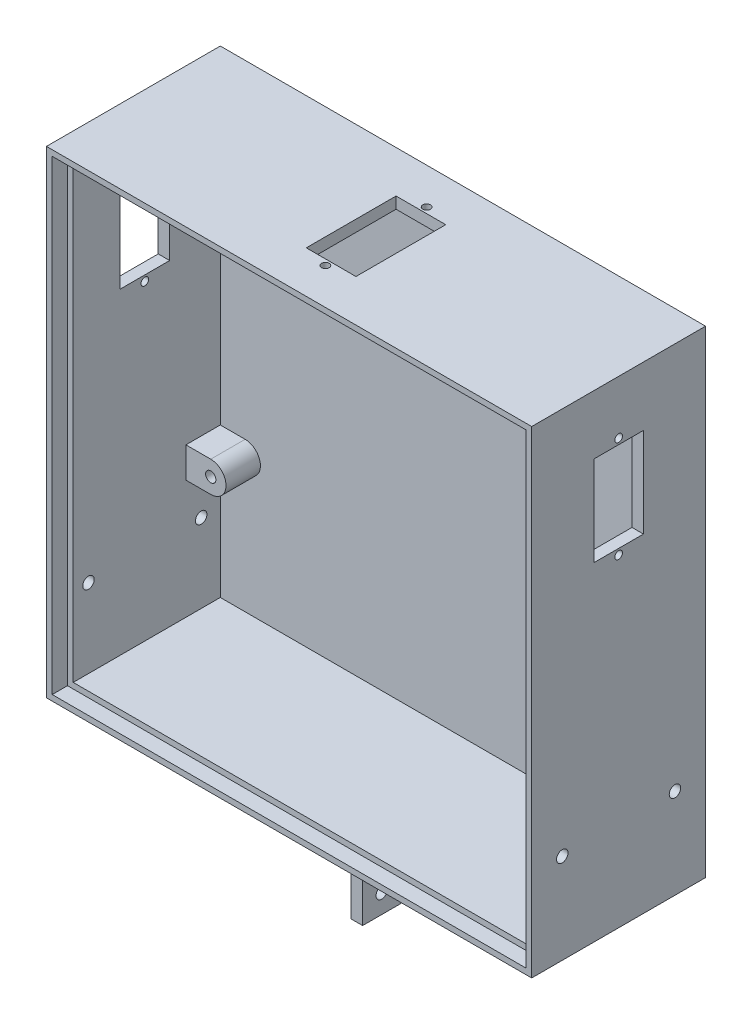
SolidWorks part; units mm, degrees
ref_plane "Front Plane" through (0, 0, 0) normal (0, 0, 1) x (1, 0, 0)
ref_plane "Top Plane" through (0, 0, 0) normal (0, 1, 0) x (1, 0, 0)
ref_plane "Right Plane" through (0, 0, 0) normal (1, 0, 0) x (0, 0, -1)
sketch "Sketch1" plane through (0, 0, 0) normal (0, 0, 1) x (1, 0, 0)
  line L1 (63.5, 62.5) -> (-63.5, 62.5)
  line L2 (63.5, 62.5) -> (63.5, -62.5)
  line L3 (63.5, -62.5) -> (-63.5, -62.5)
  line L4 (-63.5, 62.5) -> (-63.5, -62.5)
  line L5 (63.5, 62.5) -> (-63.5, -62.5) construction
  line L6 (63.5, -62.5) -> (-63.5, 62.5) construction
  point P0 (0, 0)
  dimension "D1" = 127
  dimension "D2" = 125
extrude "Boss-Extrude1" add sketch "Sketch1" along normal blind 45.5
sketch "Sketch2" plane through (0, 0, 45.5) normal (0, 0, 1) x (1, 0, 0)
  line L0 (-63.5, 62.5) -> (-63.5, -62.5) construction
  line L1 (60.5, 59.5) -> (-60.5, 59.5)
  line L2 (60.5, 59.5) -> (60.5, -59.5)
  line L3 (60.5, -59.5) -> (-60.5, -59.5)
  line L4 (-60.5, 59.5) -> (-60.5, -59.5)
  line L5 (60.5, 59.5) -> (-60.5, -59.5) construction
  line L6 (60.5, -59.5) -> (-60.5, 59.5) construction
  line L7 (63.5, 62.5) -> (-63.5, 62.5) construction
  line L9 (62, 61) -> (-62, 61)
  line L10 (62, 61) -> (62, -61)
  line L11 (62, -61) -> (-62, -61)
  line L12 (-62, 61) -> (-62, -61)
  line L13 (62, 61) -> (-62, -61) construction
  line L14 (62, -61) -> (-62, 61) construction
  point P0 (0, 0)
  point P10 (0, 0)
  dimension "D1" = 3
  dimension "D2" = 3
  dimension "D3" = 1.5
  dimension "D4" = 1.5
extrude "Cut-Extrude1" cut sketch "Sketch2" against normal offset from surface (42.5 mm away) 3 contours L1 L4 L3 L2 region at (0, 0, 45.5) up to face at (0, 0, 0)
extrude "Cut-Extrude2" cut sketch "Sketch2<3>" against normal blind 4
sketch "Sketch2<3>" plane through (0, 0, 45.5) normal (0, 0, 1) x (1, 0, 0) same geometry as "Sketch2"
sketch "Sketch3" plane through (0, 0, 3) normal (0, 0, 1) x (1, 0, 0)
  line L0 (35, 53) -> (35, 59.5)
  line L1 (60.5, 59.5) -> (-60.5, 59.5) construction
  line L2 (43, 53) -> (43, 59.5)
  line L3 (60.5, 59.5) -> (-60.5, 59.5) construction
  line L4 (0, -25.025) -> (0, 25.025) construction
  arc A0 (35, 53) -> (43, 53) centre (39, 53) ccw
  circle A2 centre (39, 53) radius 1.35
  line M3 (60.5, 59.5) -> (-60.5, 59.5)
  dimension "D2" = 4
  dimension "D3" = 2.7
  dimension "D1" = 6.5
  dimension "D4" = 39
extrude "Boss-Extrude2" add sketch "Sketch3" along normal blind 9 contours L0 A0 L2 A2 M3 region at (39, 54.7692, 3)
mirror "Mirror1" about plane through (0, 0, 0) normal (1, 0, 0) of "Boss-Extrude2"
sketch "Sketch4" plane through (0, 0, 3) normal (0, 0, 1) x (1, 0, 0)
  line L0 (54, -20.4) -> (60.5, -20.4)
  line L1 (60.5, 59.5) -> (60.5, -59.5) construction
  line L2 (54, -28.4) -> (60.5, -28.4)
  arc A0 (54, -20.4) -> (54, -28.4) centre (54, -24.4) ccw
  circle A1 centre (54, -24.4) radius 1.35
  circle A2 centre (39, 53) radius 1.35 construction
  line M9 (60.5, -59.5) -> (60.5, 59.5)
  dimension "D2" = 4
  dimension "D3" = 2.7
  dimension "D4" = 77.4
  dimension "D1" = 6.5
extrude "Boss-Extrude3" add sketch "Sketch4" along normal blind 9 contours L0 A0 L2 A1 M9 region at (55.7692, -24.4, 3)
mirror "Mirror2" about plane through (0, 0, 0) normal (1, 0, 0) of "Boss-Extrude3"
sketch "Sketch5" plane through (0, 62.5, 0) normal (0, 1, 0) x (1, 0, 0)
  line L0 (0, -22.75) -> (6.5, -22.75) construction
  line L1 (6.5, -11) -> (-6.5, -11)
  line L2 (6.5, -11) -> (6.5, -34.5)
  line L3 (6.5, -34.5) -> (-6.5, -34.5)
  line L4 (-6.5, -11) -> (-6.5, -34.5)
  line L5 (6.5, -11) -> (-6.5, -34.5) construction
  line L6 (6.5, -34.5) -> (-6.5, -11) construction
  line L7 (63.5, -45.5) -> (63.5, 0) construction
  circle A0 centre (0, -9.5) radius 1
  circle A1 centre (0, -36) radius 1
  point P0 (0, -22.75)
  point P8 (0, -11)
  point P12 (63.5, -22.75)
  dimension "D3" = 2
  dimension "D1" = 13
  dimension "D2" = 23.5
  dimension "D4" = 1.5
extrude "Cut-Extrude5" cut sketch "Sketch5" against normal up to surface (3 mm away) up to face at (0, 59.5, 12.4167)
sketch "Sketch7" plane through (63.5, 0, 0) normal (1, 0, 0) x (0, 0, -1)
  line L0 (-45.5, 62.5) -> (0, 62.5) construction
  line L1 (-16.25, 47) -> (-29.25, 47)
  line L2 (-16.25, 47) -> (-16.25, 23.5)
  line L3 (-16.25, 23.5) -> (-29.25, 23.5)
  line L4 (-29.25, 47) -> (-29.25, 23.5)
  line L5 (-16.25, 47) -> (-29.25, 23.5) construction
  line L6 (-16.25, 23.5) -> (-29.25, 47) construction
  line L8 (-22.75, 35.25) -> (-16.25, 35.25) construction
  circle A0 centre (-22.75, 48.5) radius 1
  circle A1 centre (-22.75, 22) radius 1
  point P0 (-22.75, 35.25)
  point P7 (-22.75, 62.5)
  dimension "D4" = 2
  dimension "D1" = 23.5
  dimension "D2" = 27.25
  dimension "D3" = 13
  dimension "D5" = 1.5
extrude "Cut-Extrude6" cut sketch "Sketch7" against normal up to surface (3 mm away) up to face at (60.5, -12.2, 14.875)
mirror "Mirror4" about plane through (0, 0, 0) normal (1, 0, 0) of "Cut-Extrude6"
sketch "Sketch8" plane through (-63.5, 0, 0) normal (-1, 0, 0) x (0, 0, 1)
  line L0 (45.5, -62.5) -> (0, -62.5) construction
  line L2 (3, -28.4) -> (3, -59.5) construction
  line L3 (22.75, -62.5) -> (22.75, 62.5) construction
  line L4 (45.5, 62.5) -> (0, 62.5) construction
  circle A0 centre (8, -38.9) radius 1.5
  circle A1 centre (37.5, -38.9) radius 1.5
  dimension "D1" = 3
  dimension "D2" = 23.6
  dimension "D3" = 5
extrude "Cut-Extrude7" cut sketch "Sketch8" against normal up to surface (127 mm away) up to face at (63.5, 21, 22.75)
sketch "Sketch9" plane through (0, -62.5, 0) normal (0, -1, 0) x (1, 0, 0)
  line L0 (-63.5, 45.5) -> (-63.5, 0) construction
  line L1 (1.5, 27.75) -> (-1.5, 27.75)
  line L2 (1.5, 27.75) -> (1.5, 17.75)
  line L3 (1.5, 17.75) -> (-1.5, 17.75)
  line L4 (-1.5, 27.75) -> (-1.5, 17.75)
  line L5 (1.5, 27.75) -> (-1.5, 17.75) construction
  line L6 (1.5, 17.75) -> (-1.5, 27.75) construction
  point P0 (0, 22.75)
  point P5 (0, 0)
  point P7 (0, 0)
  point P10 (-63.5, 22.75)
  dimension "D1" = 3
  dimension "D2" = 10
extrude "Boss-Extrude4" add sketch "Sketch9" along normal blind 28
sketch "Sketch10" plane through (-1.5, 0, 0) normal (-1, 0, 0) x (0, 0, 1)
  line L0 (27.75, -90.5) -> (17.75, -90.5) construction
  circle A0 centre (22.75, -85.5) radius 1.5
  point P4 (0, 0)
  point P5 (22.75, -90.5)
  dimension "D2" = 3
  dimension "D1" = 5
extrude "Cut-Extrude8" cut sketch "Sketch10" against normal up to surface (3 mm away) up to face at (1.5, -76.5, 22.75)
